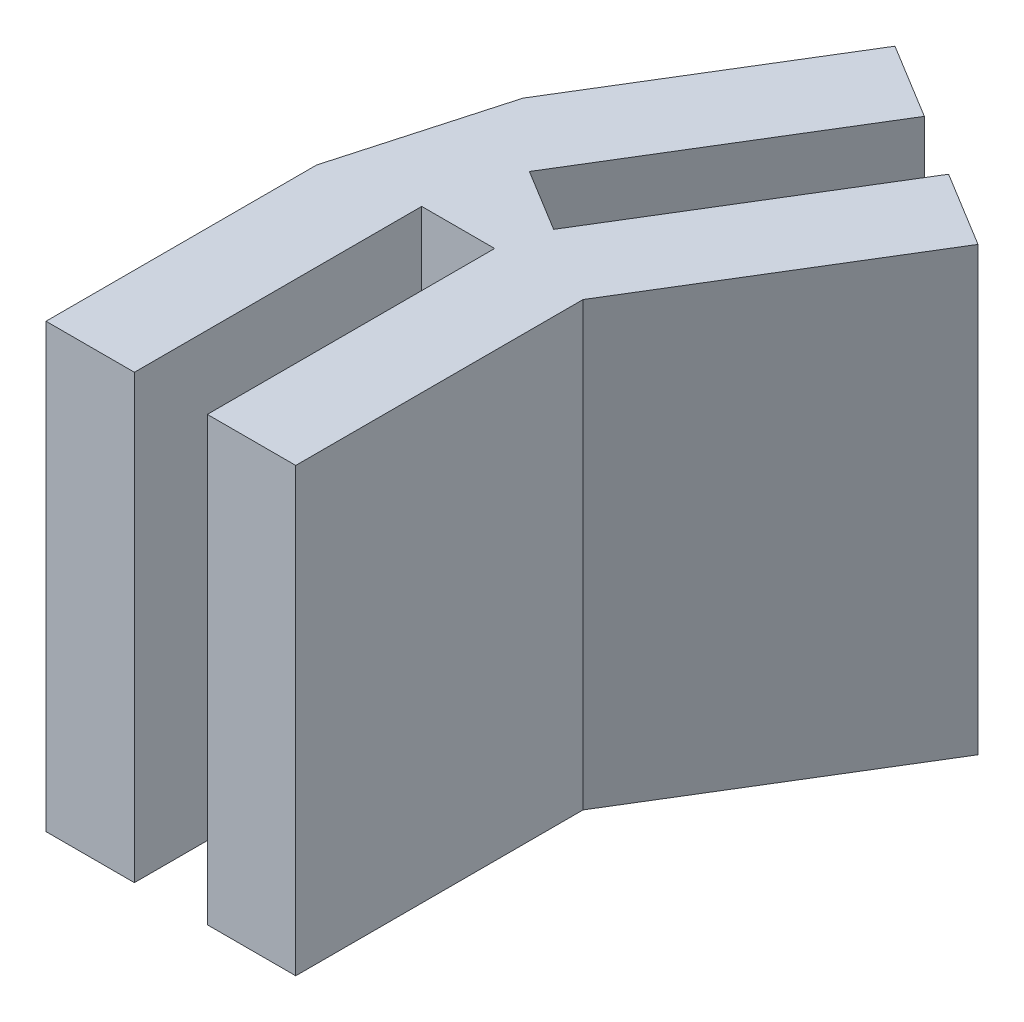
SolidWorks part; units mm, degrees
ref_plane "Front Plane" through (0, 0, 0) normal (0, 0, 1) x (1, 0, 0)
ref_plane "Top Plane" through (0, 0, 0) normal (0, 1, 0) x (1, 0, 0)
ref_plane "Right Plane" through (0, 0, 0) normal (1, 0, 0) x (0, 0, -1)
sketch "Sketch1" plane through (0, 0, 0) normal (0, 1, 0) x (1, 0, 0)
  line L0 (0, 0) -> (4, 0)
  line L1 (4, 0) -> (4, 13)
  line L2 (4, 13) -> (7.3, 13)
  line L3 (7.3, 13) -> (7.3, 0)
  line L4 (7.3, 0) -> (11.3, 0)
  line L5 (11.3, 0) -> (11.3, 13)
  line L6 (0, 0) -> (0, 16.1763)
  line L7 (11.3, 13) -> (0, 16.1763)
extrude "Boss-Extrude1" add sketch "Sketch1" along normal blind 20
mirror "Mirror1" about plane through (11.3, 20, -13) normal (-0.2706, 0, 0.9627) of "Boss-Extrude1"
fillet "Chamfer1" radius 14 1 edges at (0, 10, -16.1763) type face fillet profile chamfer first side face at (0, 10, -8.0881) second side face at (4.214, 10, -23.0799)
